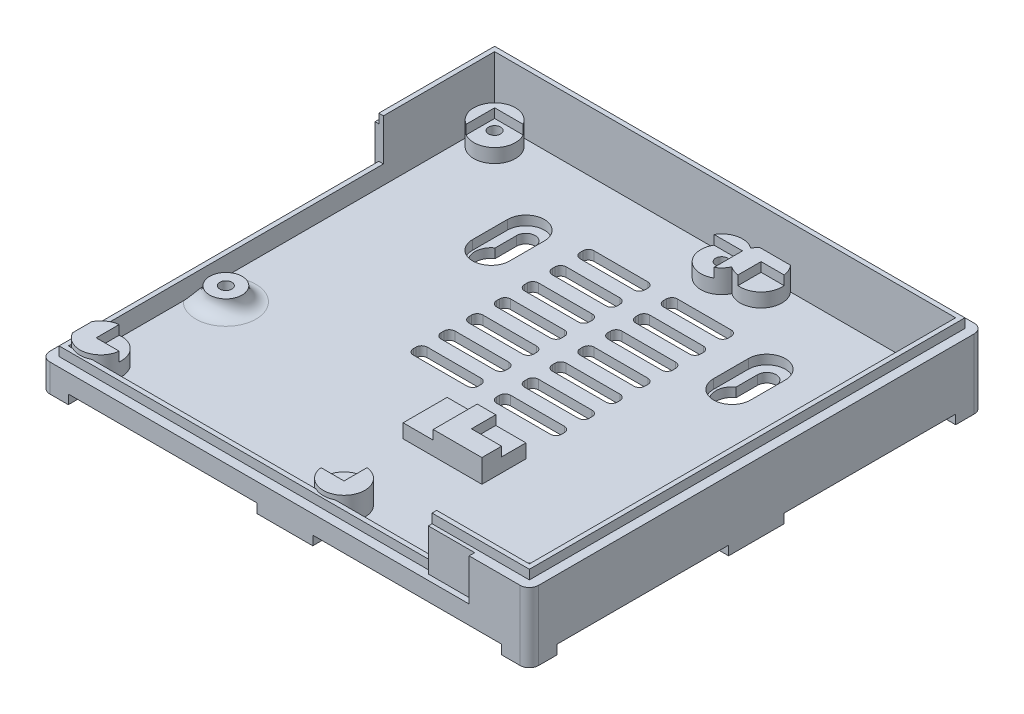
SolidWorks part; units mm, degrees
ref_plane "Alzado" through (0, 0, 0) normal (0, 0, 1) x (1, 0, 0)
ref_plane "Planta" through (0, 0, 0) normal (0, 1, 0) x (1, 0, 0)
ref_plane "Vista lateral" through (0, 0, 0) normal (1, 0, 0) x (0, 0, -1)
sketch "Croquis1" plane through (0, 0, 0) normal (0, 1, 0) x (1, 0, 0)
  line L1 (-24.5, -29) -> (24.5, -29) construction
  line L2 (-24.5, -29) -> (-24.5, 29) construction
  line L3 (-24.5, 29) -> (24.5, 29) construction
  line L4 (24.5, -29) -> (24.5, 29) construction
  line L5 (-24.5, -29) -> (24.5, 29) construction
  line L6 (-24.5, 29) -> (24.5, -29) construction
  line L7 (-26.25, 30.75) -> (26.25, 30.75) construction
  line L8 (-26.25, 30.75) -> (-26.25, -54.25) construction
  line L9 (-26.25, -54.25) -> (26.25, -54.25) construction
  line L10 (26.25, 30.75) -> (26.25, -54.25) construction
  line L11 (31.25, 30.75) -> (67.25, 30.75) construction
  line L12 (31.25, 30.75) -> (31.25, -30.75) construction
  line L13 (31.25, -30.75) -> (67.25, -30.75) construction
  line L14 (67.25, 30.75) -> (67.25, -30.75) construction
  line L15 (14.25, -4.75) -> (-1.75, -4.75) construction
  line L16 (14.25, -4.75) -> (14.25, 11.25) construction
  line L17 (14.25, 11.25) -> (-1.75, 11.25) construction
  line L18 (-1.75, -4.75) -> (-1.75, 11.25) construction
  line L19 (14.25, -4.75) -> (-1.75, 11.25) construction
  line L20 (14.25, 11.25) -> (-1.75, -4.75) construction
  line L21 (-28.75, 32.85) -> (26.25, 32.85) construction
  line L22 (-28.75, 32.85) -> (-28.75, -57.25) construction
  line L23 (-28.75, -57.25) -> (26.25, -57.25) construction
  line L24 (26.25, 32.85) -> (26.25, -57.25) construction
  line L25 (-23.25, -16.25) -> (-7.25, -16.25) construction
  circle A0 centre (49.25, -25.25) radius 1 construction
  circle A1 centre (36.75, 25.25) radius 1 construction
  point P0 (0, 0)
  point P18 (6.25, 3.25)
  dimension "D12" = 2
  dimension "D15" = 2
  dimension "D1" = 58
  dimension "D2" = 49
  dimension "D3" = 1.75
  dimension "D4" = 1.75
  dimension "D5" = 1.75
  dimension "D6" = 85
  dimension "D7" = 36
  dimension "D8" = 61.5
  dimension "D9" = 5
  dimension "D10" = 18
  dimension "D11" = 5.5
  dimension "D13" = 5.5
  dimension "D14" = 5.5
  dimension "D16" = 25.75
  dimension "D17" = 32.5
  dimension "D18" = 16
  dimension "D19" = 16
  dimension "D20" = 2.1
  dimension "D21" = 2.5
  dimension "D22" = 3
  dimension "D23" = 47
  dimension "D24" = 3
  dimension "D25" = 16
sketch "Croquis2" plane through (0, 0, 0) normal (0, 1, 0) x (1, 0, 0)
  line L0 (-26.25, 30.75) -> (-26.25, -54.25) construction
  line L1 (-29.25, 33.75) -> (70.25, 33.75) construction
  line L2 (-29.25, 33.75) -> (-29.25, -58.25) construction
  line L3 (-29.25, -58.25) -> (70.25, -58.25) construction
  line L4 (70.25, 33.75) -> (70.25, -58.25) construction
  line L5 (-26.25, 30.75) -> (26.25, 30.75) construction
  line L6 (-26.25, -54.25) -> (26.25, -54.25) construction
  line L7 (67.25, 30.75) -> (67.25, -30.75) construction
  line L9 (-30.25, 36.75) -> (71.25, 36.75)
  line L10 (-32.25, 34.75) -> (-32.25, -59.25)
  line L11 (-30.25, -61.25) -> (71.25, -61.25)
  line L12 (73.25, 34.75) -> (73.25, -59.25)
  arc A0 (-32.25, -59.25) -> (-30.25, -61.25) centre (-30.25, -59.25) ccw
  arc A1 (71.25, -61.25) -> (73.25, -59.25) centre (71.25, -59.25) ccw
  arc A2 (71.25, 36.75) -> (73.25, 34.75) centre (71.25, 34.75) cw
  arc A3 (-30.25, 36.75) -> (-32.25, 34.75) centre (-30.25, 34.75) ccw
  dimension "D9" = 2
  dimension "D1" = 3
  dimension "D2" = 3
  dimension "D3" = 4
  dimension "D4" = 3
  dimension "D5" = 3
  dimension "D6" = 3
  dimension "D7" = 3
  dimension "D8" = 3
extrude "Saliente-Extruir1" add sketch "Croquis2" along normal blind 2
sketch "Croquis3" plane through (0, 2, 0) normal (0, 1, 0) x (1, 0, 0)
  line L0 (-30.25, -59.25) -> (-13.9519, -42.9519) construction
  line L1 (-26.25, -58.25) -> (-26.25, -61.25)
  line L2 (-29.25, -55.25) -> (-32.25, -55.25)
  line L3 (-32.25, -12.25) -> (-75.7866, -12.25) construction
  line L4 (-30.25, -61.25) -> (71.25, -61.25)
  line L5 (73.25, -59.25) -> (73.25, 34.75)
  line L6 (71.25, 36.75) -> (-30.25, 36.75)
  line L7 (-32.25, 34.75) -> (-32.25, -59.25)
  line L8 (-30.25, -61.25) -> (-26.25, -61.25)
  line L11 (-32.25, -55.25) -> (-32.25, -59.25)
  line L12 (-32.25, 34.75) -> (-32.25, -59.25) construction
  line L13 (20.5, -61.25) -> (20.5, -88.5683) construction
  line L14 (-30.25, -61.25) -> (71.25, -61.25) construction
  line L15 (-32.25, 30.75) -> (-32.25, 34.75)
  line L16 (-29.25, 30.75) -> (-32.25, 30.75)
  line L17 (-26.25, 33.75) -> (-26.25, 36.75)
  line L18 (-30.25, 36.75) -> (-26.25, 36.75)
  line L19 (73.25, -55.25) -> (73.25, -59.25)
  line L20 (70.25, -55.25) -> (73.25, -55.25)
  line L21 (67.25, -58.25) -> (67.25, -61.25)
  line L22 (71.25, -61.25) -> (67.25, -61.25)
  line L23 (70.25, 30.75) -> (73.25, 30.75)
  line L24 (67.25, 33.75) -> (67.25, 36.75)
  line L25 (71.25, 36.75) -> (67.25, 36.75)
  line L26 (73.25, 30.75) -> (73.25, 34.75)
  arc A0 (-29.25, -55.25) -> (-26.25, -58.25) centre (-26.25, -55.25) ccw
  arc A1 (-29.25, 30.75) -> (-26.25, 33.75) centre (-26.25, 30.75) cw
  arc A2 (-32.25, 34.75) -> (-30.25, 36.75) centre (-30.25, 34.75) cw
  arc A3 (70.25, -55.25) -> (67.25, -58.25) centre (67.25, -55.25) cw
  arc A4 (-32.25, -59.25) -> (-30.25, -61.25) centre (-30.25, -59.25) ccw
  arc A5 (71.25, -61.25) -> (73.25, -59.25) centre (71.25, -59.25) ccw
  arc A6 (73.25, 34.75) -> (71.25, 36.75) centre (71.25, 34.75) ccw
  arc A7 (-30.25, 36.75) -> (-32.25, 34.75) centre (-30.25, 34.75) ccw
  arc A8 (-32.25, -59.25) -> (-30.25, -61.25) centre (-30.25, -59.25) ccw
  arc A12 (73.25, -59.25) -> (71.25, -61.25) centre (71.25, -59.25) cw
  arc A13 (70.25, 30.75) -> (67.25, 33.75) centre (67.25, 30.75) ccw
  arc A14 (73.25, 34.75) -> (71.25, 36.75) centre (71.25, 34.75) ccw
  point P23 (20.5, -12.25)
  dimension "D3" = 6
  dimension "D2" = 45
  dimension "D4" = 6
  dimension "D1" = 0
extrude "Saliente-Extruir2" add sketch "Croquis3" against normal blind 4
sketch "Croquis4" plane through (0, 2, 0) normal (0, 1, 0) x (1, 0, 0)
  line L0 (-32.25, -12.25) -> (73.25, -12.25) construction
  line L1 (-32.25, 34.75) -> (-32.25, -59.25) construction
  line L2 (20.5, 36.75) -> (20.5, -61.25) construction
  line L3 (71.25, 36.75) -> (-30.25, 36.75) construction
  line L5 (-32.25, -18.25) -> (-29.25, -18.25)
  line L6 (-32.25, -18.25) -> (-32.25, -6.25)
  line L7 (-32.25, -6.25) -> (-29.25, -6.25)
  line L8 (-29.25, -18.25) -> (-29.25, -6.25)
  line L9 (73.25, -6.25) -> (70.25, -6.25)
  line L10 (70.25, -18.25) -> (70.25, -6.25)
  line L11 (73.25, -18.25) -> (70.25, -18.25)
  line L12 (73.25, -18.25) -> (73.25, -6.25)
  line L13 (-30.25, -61.25) -> (71.25, -61.25) construction
  line L14 (14.5, -61.25) -> (26.5, -61.25)
  line L15 (14.5, -61.25) -> (14.5, -58.25)
  line L16 (14.5, -58.25) -> (26.5, -58.25)
  line L17 (26.5, -61.25) -> (26.5, -58.25)
  line L19 (14.5, 33.75) -> (26.5, 33.75)
  line L20 (26.5, 36.75) -> (26.5, 33.75)
  line L21 (14.5, 36.75) -> (26.5, 36.75)
  line L22 (14.5, 36.75) -> (14.5, 33.75)
  line L23 (73.25, -59.25) -> (73.25, 34.75) construction
  line L24 (-6.5, 20.75) -> (-4.5, 20.75) construction
  line L25 (-5.5, 22.75) -> (-5.5, 3.75) construction
  line L26 (44.5, 22.75) -> (48.5, 22.75)
  line L27 (-3.5, 3.75) -> (-7.5, 3.75)
  line L28 (1.5, 8.75) -> (1.5, 17.75)
  line L29 (-3.5, 22.75) -> (-7.5, 22.75)
  line L30 (-12.5, 8.75) -> (-12.5, 17.75)
  line L31 (1.5, 3.75) -> (-12.5, 22.75) construction
  line L32 (1.5, 22.75) -> (-12.5, 3.75) construction
  line L33 (53.5, 8.75) -> (53.5, 17.75)
  line L34 (44.5, 3.75) -> (48.5, 3.75)
  line L35 (39.5, 8.75) -> (39.5, 17.75)
  arc A1 (1.5, 17.75) -> (-3.5, 22.75) centre (-3.5, 17.75) ccw
  arc A2 (-7.5, 22.75) -> (-12.5, 17.75) centre (-7.5, 17.75) ccw
  arc A3 (-7.5, 3.75) -> (-12.5, 8.75) centre (-7.5, 8.75) cw
  arc A4 (-3.5, 3.75) -> (1.5, 8.75) centre (-3.5, 8.75) ccw
  arc A5 (48.5, 22.75) -> (53.5, 17.75) centre (48.5, 17.75) cw
  arc A6 (48.5, 3.75) -> (53.5, 8.75) centre (48.5, 8.75) ccw
  arc A7 (39.5, 17.75) -> (44.5, 22.75) centre (44.5, 17.75) cw
  arc A8 (44.5, 3.75) -> (39.5, 8.75) centre (44.5, 8.75) cw
  circle A9 centre (20.5, -38.25) radius 6
  point P8 (20.5, -12.25)
  point P15 (-32.25, -12.25)
  point P28 (20.5, -61.25)
  point P37 (-5.5, 13.25)
  dimension "D1" = 26
  dimension "D7" = 5
  dimension "D10" = 12
  dimension "D2" = 12
  dimension "D3" = 12
  dimension "D4" = 3
  dimension "D5" = 19
  dimension "D6" = 14
  dimension "D8" = 2
  dimension "D9" = 16
  dimension "D11" = 26
  dimension "D12" = 3
extrude "Saliente-Extruir3" add sketch "Croquis4" against normal blind 4
sketch "Croquis5" plane through (0, -2, 0) normal (0, -1, 0) x (-1, 0, 0)
  line L0 (-20.5, 33.75) -> (-20.5, -8.6005) construction
  line L1 (-26.5, 33.75) -> (-14.5, 33.75) construction
  line L2 (5.5, 18.75) -> (5.5, 5.75) construction
  line L3 (7.5, 22.75) -> (3.5, 22.75) construction
  line L6 (3.5, 16.75) -> (3.5, 12.1223)
  line L7 (7.5, 16.75) -> (7.5, 12.1223)
  line L8 (-44.5, 16.75) -> (-44.5, 12.1223)
  line L9 (-48.5, 16.75) -> (-48.5, 12.1223)
  line L10 (7.5, 3.75) -> (3.5, 3.75) construction
  line L11 (3.5, 22.75) -> (7.5, 22.75) construction
  arc A0 (3.5, 12.1223) -> (7.5, 12.1223) centre (5.5, 9.25) ccw
  arc A1 (7.5, 16.75) -> (3.5, 16.75) centre (5.5, 16.75) ccw
  arc A2 (-48.5, 16.75) -> (-44.5, 16.75) centre (-46.5, 16.75) cw
  arc A3 (-44.5, 12.1223) -> (-48.5, 12.1223) centre (-46.5, 9.25) cw
  point P8 (5.5, 22.75)
  dimension "D3" = 7
  dimension "D4" = 4
  dimension "D1" = 2
  dimension "D2" = 4
extrude "Cortar-Extruir1" cut sketch "Croquis5" against normal blind 7
sketch "Croquis6" plane through (0, 2, 0) normal (0, 1, 0) x (1, 0, 0)
  line L0 (-9.5, 9.25) -> (-9.5, 16.75)
  line L1 (-1.5, 9.25) -> (-1.5, 16.75)
  line L2 (20.5, 36.75) -> (20.5, 6.9246) construction
  line L3 (26.5, 36.75) -> (14.5, 36.75) construction
  line L4 (42.5, 9.25) -> (42.5, 16.75)
  line L5 (50.5, 9.25) -> (50.5, 16.75)
  arc A0 (-9.5, 9.25) -> (-1.5, 9.25) centre (-5.5, 9.25) ccw
  arc A1 (-1.5, 16.75) -> (-9.5, 16.75) centre (-5.5, 16.75) ccw
  arc A2 (-3.5, 16.75) -> (-7.5, 16.75) centre (-5.5, 16.75) ccw construction
  arc A3 (50.5, 9.25) -> (42.5, 9.25) centre (46.5, 9.25) cw
  arc A4 (42.5, 16.75) -> (50.5, 16.75) centre (46.5, 16.75) cw
  point P5 (-5.5, 18.75)
  point P6 (-5.5, 20.75)
  dimension "D1" = 8
  dimension "D2" = 8
  dimension "D3" = 2
extrude "Cortar-Extruir3" cut sketch "Croquis6" against normal blind 2
sketch "Croquis7" plane through (0, 2, 0) normal (0, -1, 0) x (-1, 0, 0)
  line L0 (-31.25, -30.75) -> (-26.25, -30.75) construction
  line L1 (-26.25, 30.75) -> (-26.25, -54.25) construction
  line L2 (-73.25, -59.25) -> (-73.25, 34.75) construction
  line L3 (-20.25, -26) -> (-37.25, -26)
  line L4 (-20.25, -26) -> (-20.25, -35.5)
  line L5 (-20.25, -35.5) -> (-37.25, -35.5)
  line L6 (-37.25, -26) -> (-37.25, -35.5)
  line L7 (-20.25, -26) -> (-37.25, -35.5) construction
  line L8 (-20.25, -35.5) -> (-37.25, -26) construction
  line L9 (30.25, -61.25) -> (-71.25, -61.25) construction
  line L10 (24.5, -29) -> (-24.5, -29) construction
  circle A0 centre (24.5, 29) radius 4.5
  arc A3 (-28.589, 27.1211) -> (-27.161, 32.6289) centre (-24.5, 29) ccw
  circle A7 centre (-65.25, -53.25) radius 4.5
  arc A8 (-27.161, 32.6289) -> (-28.589, 27.1211) centre (-31.25, 30.75) ccw
  circle A9 centre (-67.25, 30.75) radius 4.5
  circle A10 centre (-67.25, -30.75) radius 4.5
  circle A11 centre (-26.25, -54.25) radius 4.5
  circle A12 centre (26.25, -54.25) radius 4.5
  circle A13 centre (24.5, -29) radius 3.5
  circle A14 centre (24.5, -29) radius 1.3
  circle A16 centre (24.5, 29) radius 1.3 construction
  point P18 (-28.75, -30.75)
  dimension "D3" = 9
  dimension "D6" = 2.6
  dimension "D7" = 7
  dimension "D1" = 3
  dimension "D2" = 6
  dimension "D4" = 8
  dimension "D5" = 8
extrude "Saliente-Extruir6" add sketch "Croquis7" against normal blind 3
sketch "Croquis8" plane through (0, 0, 0) normal (0, -1, 0) x (1, 0, 0)
  circle A0 centre (-24.5, -29) radius 1.3
  circle A1 centre (24.5, -29) radius 1.3
  circle A2 centre (65.25, 53.25) radius 1.3
  dimension "D1" = 2.6
extrude "Cortar-Extruir4" cut sketch "Croquis8" against normal blind 19
sketch "Croquis9" plane through (0, 5, 0) normal (0, 1, 0) x (1, 0, 0)
  line L0 (37.25, -35.5) -> (37.25, -26) construction
  line L1 (37.25, -26) -> (20.25, -26) construction
  line L3 (20.25, -35.5) -> (37.25, -35.5) construction
  line L4 (37.25, -35.5) -> (37.25, -31.25)
  line L5 (30.75, -26) -> (26.75, -26)
  line L7 (26.75, -35.5) -> (37.25, -35.5)
  line L8 (-26.75, -49.7779) -> (-26.75, -54.75)
  line L9 (-26.75, -54.75) -> (-21.7779, -54.75)
  line L10 (21.7779, -54.75) -> (26.75, -54.75)
  line L11 (26.75, -54.75) -> (26.75, -49.7779)
  line L12 (26.75, -26) -> (26.75, -35.5)
  line L13 (30.75, -26) -> (30.75, -31.25)
  line L14 (30.75, -31.25) -> (37.25, -31.25)
  line L15 (62.7779, -31.25) -> (67.75, -31.25)
  line L16 (67.75, -31.25) -> (67.75, -26.2779)
  line L17 (62.7779, 31.25) -> (67.75, 31.25)
  line L18 (67.75, 31.25) -> (67.75, 26.2779)
  line L19 (20.6029, 31.25) -> (26.75, 31.25)
  line L20 (26.75, 31.25) -> (26.75, 25.1029)
  line L21 (30.75, 26.2779) -> (30.75, 31.25)
  line L22 (30.75, 31.25) -> (35.7221, 31.25)
  line L23 (-26.75, 25.1029) -> (-26.75, 31.25)
  line L24 (-26.75, 31.25) -> (-20.6029, 31.25)
  line L25 (-26.25, 30.75) -> (-26.25, -54.25) construction
  line L26 (-26.25, -54.25) -> (26.25, -54.25) construction
  line L27 (26.25, 30.75) -> (26.25, -54.25) construction
  line L28 (31.25, -30.75) -> (67.25, -30.75) construction
  line L29 (31.25, 30.75) -> (31.25, -30.75) construction
  line L30 (67.25, 30.75) -> (67.25, -30.75) construction
  line L31 (31.25, 30.75) -> (67.25, 30.75) construction
  line L32 (-26.25, 30.75) -> (26.25, 30.75) construction
  arc A0 (28.589, 27.1211) -> (27.161, 32.6289) centre (31.25, 30.75) ccw construction
  arc A1 (27.161, 32.6289) -> (28.589, 27.1211) centre (24.5, 29) ccw construction
  circle A2 centre (67.25, 30.75) radius 4.5 construction
  circle A3 centre (67.25, -30.75) radius 4.5 construction
  circle A4 centre (26.25, -54.25) radius 4.5 construction
  circle A5 centre (-26.25, -54.25) radius 4.5 construction
  circle A6 centre (-24.5, 29) radius 4.5 construction
  arc A7 (28.589, 27.1211) -> (30.75, 26.2779) centre (31.25, 30.75) ccw
  arc A8 (27.161, 32.6289) -> (20.6029, 31.25) centre (24.5, 29) ccw
  arc A9 (67.75, 26.2779) -> (62.7779, 31.25) centre (67.25, 30.75) ccw
  arc A10 (62.7779, -31.25) -> (67.75, -26.2779) centre (67.25, -30.75) ccw
  arc A11 (21.7779, -54.75) -> (26.75, -49.7779) centre (26.25, -54.25) ccw
  arc A12 (-26.75, -49.7779) -> (-21.7779, -54.75) centre (-26.25, -54.25) ccw
  arc A13 (-20.6029, 31.25) -> (-26.75, 25.1029) centre (-24.5, 29) ccw
  arc A14 (26.75, 25.1029) -> (28.589, 27.1211) centre (24.5, 29) ccw
  arc A15 (35.7221, 31.25) -> (27.161, 32.6289) centre (31.25, 30.75) ccw
  dimension "D1" = 0.5
  dimension "D2" = 0.5
  dimension "D3" = 0.5
  dimension "D4" = 0.5
  dimension "D5" = 0.5
  dimension "D6" = 0.5
  dimension "D7" = 0.5
  dimension "D8" = 0.5
  dimension "D9" = 0.5
  dimension "D10" = 0.5
  dimension "D11" = 0.5
  dimension "D12" = 0.5
  dimension "D13" = 0.5
  dimension "D14" = 0.5
extrude "Saliente-Extruir7" add sketch "Croquis9" along normal blind 2
sketch "Croquis10" plane through (0, 5, 0) normal (0, 1, 0) x (1, 0, 0)
  circle A0 centre (65.25, -53.25) radius 4.5 construction
  circle A1 centre (65.25, -53.25) radius 1.3 construction
  circle A2 centre (65.25, -53.25) radius 4.5
  circle A3 centre (65.25, -53.25) radius 1.3
extrude "Saliente-Extruir8" add sketch "Croquis10" along normal blind 2
sketch "Croquis11" plane through (0, 2, 0) normal (0, 1, 0) x (1, 0, 0)
  line L0 (20.5, 36.75) -> (20.5, -15.13) construction
  line L1 (71.25, 36.75) -> (-30.25, 36.75) construction
  line L2 (35.3, 17.25) -> (23.7, 17.25)
  line L3 (5.7, 20.25) -> (17.3, 20.25)
  line L4 (4.5, 19.05) -> (4.5, 18.45)
  line L5 (5.7, 17.25) -> (17.3, 17.25)
  line L6 (18.5, 19.05) -> (18.5, 18.45)
  line L7 (4.5, 20.25) -> (18.5, 17.25) construction
  line L8 (4.5, 17.25) -> (18.5, 20.25) construction
  line L9 (22.5, 19.05) -> (22.5, 18.45)
  line L10 (35.3, 20.25) -> (23.7, 20.25)
  line L11 (36.5, 19.05) -> (36.5, 18.45)
  line L12 (4.5, 13.05) -> (4.5, 12.45)
  line L13 (5.7, 14.25) -> (17.3, 14.25)
  line L14 (18.5, 13.05) -> (18.5, 12.45)
  line L15 (5.7, 11.25) -> (17.3, 11.25)
  line L16 (35.3, 11.25) -> (23.7, 11.25)
  line L17 (22.5, 13.05) -> (22.5, 12.45)
  line L18 (35.3, 14.25) -> (23.7, 14.25)
  line L19 (36.5, 13.05) -> (36.5, 12.45)
  line L20 (4.5, 7.05) -> (4.5, 6.45)
  line L21 (5.7, 8.25) -> (17.3, 8.25)
  line L22 (18.5, 7.05) -> (18.5, 6.45)
  line L23 (5.7, 5.25) -> (17.3, 5.25)
  line L24 (35.3, 5.25) -> (23.7, 5.25)
  line L25 (22.5, 7.05) -> (22.5, 6.45)
  line L26 (35.3, 8.25) -> (23.7, 8.25)
  line L27 (36.5, 7.05) -> (36.5, 6.45)
  line L28 (4.5, 1.05) -> (4.5, 0.45)
  line L29 (5.7, 2.25) -> (17.3, 2.25)
  line L30 (18.5, 1.05) -> (18.5, 0.45)
  line L31 (5.7, -0.75) -> (17.3, -0.75)
  line L32 (35.3, -0.75) -> (23.7, -0.75)
  line L33 (22.5, 1.05) -> (22.5, 0.45)
  line L34 (35.3, 2.25) -> (23.7, 2.25)
  line L35 (36.5, 1.05) -> (36.5, 0.45)
  line L36 (4.5, -4.95) -> (4.5, -5.55)
  line L37 (5.7, -3.75) -> (17.3, -3.75)
  line L38 (18.5, -4.95) -> (18.5, -5.55)
  line L39 (5.7, -6.75) -> (17.3, -6.75)
  line L40 (35.3, -6.75) -> (23.7, -6.75)
  line L41 (22.5, -4.95) -> (22.5, -5.55)
  line L42 (35.3, -3.75) -> (23.7, -3.75)
  line L43 (36.5, -4.95) -> (36.5, -5.55)
  line L44 (4.5, -10.95) -> (4.5, -11.55)
  line L45 (5.7, -9.75) -> (17.3, -9.75)
  line L46 (18.5, -10.95) -> (18.5, -11.55)
  line L47 (5.7, -12.75) -> (17.3, -12.75)
  line L48 (35.3, -12.75) -> (23.7, -12.75)
  line L49 (22.5, -10.95) -> (22.5, -11.55)
  line L50 (35.3, -9.75) -> (23.7, -9.75)
  line L51 (36.5, -10.95) -> (36.5, -11.55)
  line L52 (4.5, -16.95) -> (4.5, -17.55)
  line L53 (5.7, -15.75) -> (17.3, -15.75)
  line L54 (18.5, -16.95) -> (18.5, -17.55)
  line L55 (5.7, -18.75) -> (17.3, -18.75)
  line L56 (35.3, -18.75) -> (23.7, -18.75)
  line L57 (22.5, -16.95) -> (22.5, -17.55)
  line L58 (35.3, -15.75) -> (23.7, -15.75)
  line L59 (36.5, -16.95) -> (36.5, -17.55)
  arc A0 (17.3, 20.25) -> (18.5, 19.05) centre (17.3, 19.05) cw
  arc A1 (17.3, 17.25) -> (18.5, 18.45) centre (17.3, 18.45) ccw
  arc A2 (4.5, 18.45) -> (5.7, 17.25) centre (5.7, 18.45) ccw
  arc A3 (5.7, 20.25) -> (4.5, 19.05) centre (5.7, 19.05) ccw
  arc A4 (23.7, 17.25) -> (22.5, 18.45) centre (23.7, 18.45) cw
  arc A5 (23.7, 20.25) -> (22.5, 19.05) centre (23.7, 19.05) ccw
  arc A6 (36.5, 18.45) -> (35.3, 17.25) centre (35.3, 18.45) cw
  arc A7 (35.3, 20.25) -> (36.5, 19.05) centre (35.3, 19.05) cw
  arc A8 (5.7, 14.25) -> (4.5, 13.05) centre (5.7, 13.05) ccw
  arc A9 (4.5, 12.45) -> (5.7, 11.25) centre (5.7, 12.45) ccw
  arc A10 (17.3, 14.25) -> (18.5, 13.05) centre (17.3, 13.05) cw
  arc A11 (17.3, 11.25) -> (18.5, 12.45) centre (17.3, 12.45) ccw
  arc A12 (23.7, 11.25) -> (22.5, 12.45) centre (23.7, 12.45) cw
  arc A13 (23.7, 14.25) -> (22.5, 13.05) centre (23.7, 13.05) ccw
  arc A14 (35.3, 14.25) -> (36.5, 13.05) centre (35.3, 13.05) cw
  arc A15 (36.5, 12.45) -> (35.3, 11.25) centre (35.3, 12.45) cw
  arc A16 (5.7, 8.25) -> (4.5, 7.05) centre (5.7, 7.05) ccw
  arc A17 (4.5, 6.45) -> (5.7, 5.25) centre (5.7, 6.45) ccw
  arc A18 (17.3, 8.25) -> (18.5, 7.05) centre (17.3, 7.05) cw
  arc A19 (17.3, 5.25) -> (18.5, 6.45) centre (17.3, 6.45) ccw
  arc A20 (23.7, 5.25) -> (22.5, 6.45) centre (23.7, 6.45) cw
  arc A21 (23.7, 8.25) -> (22.5, 7.05) centre (23.7, 7.05) ccw
  arc A22 (35.3, 8.25) -> (36.5, 7.05) centre (35.3, 7.05) cw
  arc A23 (36.5, 6.45) -> (35.3, 5.25) centre (35.3, 6.45) cw
  arc A24 (5.7, 2.25) -> (4.5, 1.05) centre (5.7, 1.05) ccw
  arc A25 (4.5, 0.45) -> (5.7, -0.75) centre (5.7, 0.45) ccw
  arc A26 (17.3, 2.25) -> (18.5, 1.05) centre (17.3, 1.05) cw
  arc A27 (17.3, -0.75) -> (18.5, 0.45) centre (17.3, 0.45) ccw
  arc A28 (23.7, -0.75) -> (22.5, 0.45) centre (23.7, 0.45) cw
  arc A29 (23.7, 2.25) -> (22.5, 1.05) centre (23.7, 1.05) ccw
  arc A30 (35.3, 2.25) -> (36.5, 1.05) centre (35.3, 1.05) cw
  arc A31 (36.5, 0.45) -> (35.3, -0.75) centre (35.3, 0.45) cw
  arc A32 (5.7, -3.75) -> (4.5, -4.95) centre (5.7, -4.95) ccw
  arc A33 (4.5, -5.55) -> (5.7, -6.75) centre (5.7, -5.55) ccw
  arc A34 (17.3, -3.75) -> (18.5, -4.95) centre (17.3, -4.95) cw
  arc A35 (17.3, -6.75) -> (18.5, -5.55) centre (17.3, -5.55) ccw
  arc A36 (23.7, -6.75) -> (22.5, -5.55) centre (23.7, -5.55) cw
  arc A37 (23.7, -3.75) -> (22.5, -4.95) centre (23.7, -4.95) ccw
  arc A38 (35.3, -3.75) -> (36.5, -4.95) centre (35.3, -4.95) cw
  arc A39 (36.5, -5.55) -> (35.3, -6.75) centre (35.3, -5.55) cw
  arc A40 (5.7, -9.75) -> (4.5, -10.95) centre (5.7, -10.95) ccw
  arc A41 (4.5, -11.55) -> (5.7, -12.75) centre (5.7, -11.55) ccw
  arc A42 (17.3, -9.75) -> (18.5, -10.95) centre (17.3, -10.95) cw
  arc A43 (17.3, -12.75) -> (18.5, -11.55) centre (17.3, -11.55) ccw
  arc A44 (23.7, -12.75) -> (22.5, -11.55) centre (23.7, -11.55) cw
  arc A45 (23.7, -9.75) -> (22.5, -10.95) centre (23.7, -10.95) ccw
  arc A46 (35.3, -9.75) -> (36.5, -10.95) centre (35.3, -10.95) cw
  arc A47 (36.5, -11.55) -> (35.3, -12.75) centre (35.3, -11.55) cw
  arc A48 (5.7, -15.75) -> (4.5, -16.95) centre (5.7, -16.95) ccw
  arc A49 (4.5, -17.55) -> (5.7, -18.75) centre (5.7, -17.55) ccw
  arc A50 (17.3, -15.75) -> (18.5, -16.95) centre (17.3, -16.95) cw
  arc A51 (17.3, -18.75) -> (18.5, -17.55) centre (17.3, -17.55) ccw
  arc A52 (23.7, -18.75) -> (22.5, -17.55) centre (23.7, -17.55) cw
  arc A53 (23.7, -15.75) -> (22.5, -16.95) centre (23.7, -16.95) ccw
  arc A54 (35.3, -15.75) -> (36.5, -16.95) centre (35.3, -16.95) cw
  arc A55 (36.5, -17.55) -> (35.3, -18.75) centre (35.3, -17.55) cw
  point P4 (11.5, 18.75)
  dimension "D4" = 1.2
  dimension "D1" = 2
  dimension "D2" = 14
  dimension "D3" = 3
  dimension "D5" = 18
  dimension "D6" = 7
extrude "Cortar-Extruir5" cut sketch "Croquis11" against normal blind 4
sketch "Croquis12" plane through (0, 2, 0) normal (0, 1, 0) x (1, 0, 0)
  line L8 (70.25, 33.75) -> (-29.25, 33.75)
  line L9 (-29.25, 33.75) -> (-29.25, -58.25)
  line L10 (-29.25, -58.25) -> (70.25, -58.25)
  line L11 (70.25, -58.25) -> (70.25, 33.75)
  line L12 (70.25, 33.75) -> (-29.25, 33.75)
  line L13 (-29.25, 33.75) -> (-29.25, -58.25)
  line L14 (-29.25, -58.25) -> (70.25, -58.25)
  line L15 (70.25, -58.25) -> (70.25, 33.75)
  line L16 (71.25, 36.75) -> (-30.25, 36.75)
  line L17 (-32.25, 34.75) -> (-32.25, -59.25)
  line L18 (-30.25, -61.25) -> (71.25, -61.25)
  line L19 (73.25, -59.25) -> (73.25, 34.75)
  line L20 (71.25, 36.75) -> (-30.25, 36.75)
  line L21 (-32.25, 34.75) -> (-32.25, -59.25)
  line L22 (-30.25, -61.25) -> (71.25, -61.25)
  line L23 (73.25, -59.25) -> (73.25, 34.75)
  arc A8 (-30.25, 36.75) -> (-32.25, 34.75) centre (-30.25, 34.75) ccw
  arc A9 (-32.25, -59.25) -> (-30.25, -61.25) centre (-30.25, -59.25) ccw
  arc A10 (71.25, -61.25) -> (73.25, -59.25) centre (71.25, -59.25) ccw
  arc A11 (73.25, 34.75) -> (71.25, 36.75) centre (71.25, 34.75) ccw
  arc A12 (-30.25, 36.75) -> (-32.25, 34.75) centre (-30.25, 34.75) ccw
  arc A13 (-32.25, -59.25) -> (-30.25, -61.25) centre (-30.25, -59.25) ccw
  arc A14 (71.25, -61.25) -> (73.25, -59.25) centre (71.25, -59.25) ccw
  arc A15 (73.25, 34.75) -> (71.25, 36.75) centre (71.25, 34.75) ccw
  dimension "D1" = 3
  dimension "D2" = 0
extrude "Saliente-Extruir9" add sketch "Croquis12" along normal blind 2
sketch "Croquis13" plane through (0, 4, 0) normal (0, 1, 0) x (1, 0, 0)
  line L0 (-32.25, 9.75) -> (-29.25, 9.75)
  line L1 (-29.25, 33.75) -> (-29.25, -50.8959) construction
  line L2 (-29.25, 9.75) -> (-29.25, 33.75)
  line L3 (-29.25, 33.75) -> (70.25, 33.75)
  line L4 (71.25, 36.75) -> (-30.25, 36.75)
  line L5 (-32.25, 34.75) -> (-32.25, -59.25)
  line L6 (-30.25, -61.25) -> (71.25, -61.25)
  line L7 (73.25, -59.25) -> (73.25, 34.75)
  line L8 (71.25, 36.75) -> (-30.25, 36.75)
  line L9 (-32.25, 34.75) -> (-32.25, 9.75)
  line L13 (70.25, -27.3959) -> (70.25, 27.3959) construction
  line L14 (63.8959, 33.75) -> (34.6041, 33.75) construction
  line L17 (73.25, -59.25) -> (73.25, 34.75) construction
  line L18 (73.25, -5.25) -> (73.25, 34.75)
  line L19 (70.25, -5.25) -> (70.25, 33.75)
  line L20 (-26.25, 30.75) -> (26.25, 30.75) construction
  line L22 (28.3116, -58.25) -> (70.25, -58.25) construction
  line L23 (-30.25, -61.25) -> (71.25, -61.25) construction
  line L24 (50.25, -58.25) -> (70.25, -58.25)
  line L25 (50.25, -61.25) -> (71.25, -61.25)
  line L26 (73.25, -5.25) -> (73.25, -59.25)
  line L27 (70.25, -5.25) -> (70.25, -58.25)
  line L28 (50.25, -58.25) -> (50.25, -61.25)
  arc A1 (71.25, -61.25) -> (73.25, -59.25) centre (71.25, -59.25) ccw construction
  arc A2 (71.25, -61.25) -> (73.25, -59.25) centre (71.25, -59.25) ccw
  arc A4 (73.25, 34.75) -> (71.25, 36.75) centre (71.25, 34.75) ccw
  arc A5 (-30.25, 36.75) -> (-32.25, 34.75) centre (-30.25, 34.75) ccw
  arc A6 (-32.25, -59.25) -> (-30.25, -61.25) centre (-30.25, -59.25) ccw
  arc A7 (71.25, -61.25) -> (73.25, -59.25) centre (71.25, -59.25) ccw
  arc A8 (73.25, 34.75) -> (71.25, 36.75) centre (71.25, 34.75) ccw
  arc A9 (-30.25, 36.75) -> (-32.25, 34.75) centre (-30.25, 34.75) ccw
  dimension "D2" = 21
  dimension "D3" = 20
  dimension "D1" = 0
extrude "Saliente-Extruir11" add sketch "Croquis13" along normal blind 9
sketch "Croquis14" plane through (0, 4, 0) normal (0, 1, 0) x (1, 0, 0)
  line L0 (-29.25, 9.75) -> (-29.25, -58.25)
  line L1 (-29.25, -58.25) -> (50.25, -58.25)
  line L2 (50.25, -58.25) -> (50.25, -59.25)
  line L3 (50.25, -58.25) -> (50.25, -61.25) construction
  line L4 (50.25, -59.25) -> (-30.25, -59.25)
  line L5 (-30.25, -59.25) -> (-30.25, 9.75)
  line L6 (-32.25, 9.75) -> (-29.25, 9.75) construction
  line L7 (-30.25, 9.75) -> (-29.25, 9.75)
  dimension "D1" = 1
  dimension "D2" = 1
extrude "Saliente-Extruir12" add sketch "Croquis14" along normal blind 2
sketch "Croquis16" plane through (0, 13, 0) normal (0, 1, 0) x (1, 0, 0)
  line L1 (-31.05, 14.75) -> (-32.25, 14.75)
  line L2 (-31.05, 14.75) -> (-31.05, 9.75)
  line L3 (-31.05, 9.75) -> (-32.25, 9.75)
  line L4 (-32.25, 14.75) -> (-32.25, 9.75)
  line L5 (-26.25, 30.75) -> (26.25, 30.75) construction
  line L6 (-30.25, -59.25) -> (-30.25, -49.7827)
  line L7 (50.25, -61.25) -> (60.25, -61.25)
  line L8 (50.25, -61.25) -> (50.25, -60.05)
  line L9 (50.25, -60.05) -> (60.25, -60.05)
  line L10 (60.25, -61.25) -> (60.25, -60.05)
  line L11 (-30.25, 9.75) -> (-30.25, -52.1884) construction
  line L12 (-30.25, -49.7827) -> (-31.05, -51.3854)
  line L13 (-31.05, -51.3854) -> (-31.05, -58.2157)
  line L14 (-31.05, -58.2157) -> (-30.25, -59.25)
  dimension "D1" = 16
  dimension "D2" = 1.2
  dimension "D3" = 1.2
  dimension "D4" = 10
extrude "Cortar-Extruir6" cut sketch "Croquis16" against normal up to surface (9 mm away) up to face at (-12.9071, 4, 43.296)
sketch "Croquis17" plane through (0, 13, 0) normal (0, 1, 0) x (1, 0, 0)
  line L0 (50.25, -58.25) -> (70.25, -58.25)
  line L1 (70.25, -58.25) -> (70.25, 33.75)
  line L2 (70.25, 33.75) -> (-29.25, 33.75)
  line L3 (-29.25, 33.75) -> (-29.25, 9.75)
  line L4 (-29.25, 9.75) -> (-30.25, 9.75)
  line L5 (-30.25, 9.75) -> (-30.25, 34.75)
  line L6 (-30.25, 34.75) -> (71.25, 34.75)
  line L7 (71.25, 34.75) -> (71.25, -59.25)
  line L8 (71.25, -59.25) -> (50.25, -59.25)
  line L9 (-29.25, 9.75) -> (-30.25, 9.75)
  line L10 (50.25, -58.25) -> (50.25, -59.25)
  line M8 (-31.05, 9.75) -> (-29.25, 9.75)
  line M9 (-29.25, 9.75) -> (-29.25, 33.75)
  line M10 (-29.25, 33.75) -> (70.25, 33.75)
  line M11 (70.25, 33.75) -> (70.25, -58.25)
  line M12 (70.25, -58.25) -> (50.25, -58.25)
  line M13 (50.25, -58.25) -> (50.25, -60.05)
  dimension "D1" = 1
extrude "Saliente-Extruir13" add sketch "Croquis17" along normal blind 2 contours L8 L7 L6 L5 M8 M9 M10 M11 M12 M13 region at (60.25, 13, 58.3883)
sketch "Croquis18" plane through (0, 5, 0) normal (0, 1, 0) x (1, 0, 0)
  circle A0 centre (-24.5, -29) radius 1.3
extrude "Cortar-Extruir7" cut sketch "Croquis18" against normal blind 10
sketch "Croquis19" plane through (0, 0, 0) normal (0, -1, 0) x (1, 0, 0)
  circle A0 centre (-24.5, -29) radius 2
  circle A1 centre (24.5, -29) radius 2
  circle A2 centre (-24.5, 29) radius 2
  circle A3 centre (65.25, 53.25) radius 2
  dimension "D1" = 4
extrude "Cortar-Extruir8" cut sketch "Croquis19" against normal blind 1.5
fillet "Redondeo1" radius 3 1 edges at (-24.5, 2, 32.5)
